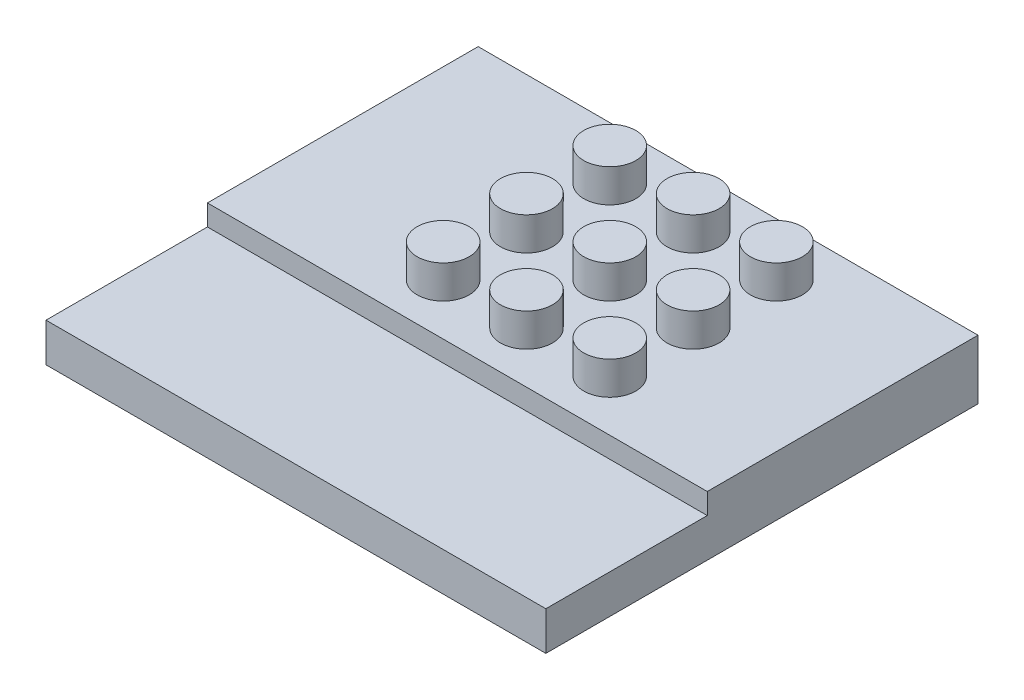
SolidWorks part; units mm, degrees
ref_plane "Front Plane" through (0, 0, 0) normal (0, 0, 1) x (1, 0, 0)
ref_plane "Top Plane" through (0, 0, 0) normal (0, 1, 0) x (1, 0, 0)
ref_plane "Right Plane" through (0, 0, 0) normal (1, 0, 0) x (0, 0, -1)
ref_plane "Plane2" through (0, 1.5875, 0) normal (0, 1, 0) x (-1, 0, 0)
sketch "Sketch3" plane through (0, 1.5875, 0) normal (0, 1, 0) x (-1, 0, 0)
  line L1 (-10.75, -16) -> (-17.5, -16)
  line L2 (-10.75, -16) -> (-10.75, -26.25)
  line L3 (-10.75, -26.25) -> (-17.5, -26.25)
  line L4 (-17.5, -16) -> (-17.5, -26.25)
extrude "Boss-Extrude2" add sketch "Sketch3" along normal blind 4.4125
sketch "Sketch5" plane through (0, 1.5875, 0) normal (0, -1, 0) x (1, 0, 0)
  circle A0 centre (16.36, -24.96) radius 1.25
  circle A1 centre (12.36, -24.96) radius 1.25
  circle A2 centre (8.36, -24.96) radius 1.25
  circle A3 centre (16.36, -20.96) radius 1.25
  circle A4 centre (12.36, -20.96) radius 1.25
  circle A5 centre (8.36, -20.96) radius 1.25
  circle A6 centre (16.36, -16.96) radius 1.25
  circle A7 centre (12.36, -16.96) radius 1.25
  circle A8 centre (8.36, -16.96) radius 1.25
  dimension "D1" = 3
  dimension "D2" = 3
extrude "Boss-Extrude3" add sketch "Sketch5" along normal blind 1.5875 and the other way blind 6
sketch "Sketch6" plane through (17.5, 0, 0) normal (1, 0, 0) x (0, 0, -1)
  line L0 (16, 6) -> (16.4473, 6) construction
  line L1 (6.75, 6) -> (27.5, 6)
  line L2 (6.75, 6) -> (6.75, 3.1425)
  line L3 (6.75, 3.1425) -> (27.5, 3.1425)
  line L4 (27.5, 6) -> (27.5, 3.1425)
extrude "Boss-Extrude4" add sketch "Sketch6" along normal blind 6
sketch "Sketch7" plane through (10.75, 0, 0) normal (-1, 0, 0) x (0, 0, 1)
  line L1 (-27.5, 6) -> (-6.75, 6)
  line L2 (-27.5, 6) -> (-27.5, 3.1425)
  line L3 (-27.5, 3.1425) -> (-6.75, 3.1425)
  line L4 (-6.75, 6) -> (-6.75, 3.1425)
extrude "Boss-Extrude5" add sketch "Sketch7" along normal blind 11.25
sketch "Sketch9" plane through (17.5, 0, 0) normal (-1, 0, 0) x (0, 0, 1)
  line L1 (-16, 6) -> (-6.75, 6)
  line L2 (-16, 6) -> (-16, 3.1425)
  line L3 (-16, 3.1425) -> (-6.75, 3.1425)
  line L4 (-6.75, 6) -> (-6.75, 3.1425)
extrude "Boss-Extrude6" add sketch "Sketch9" along normal up to next
sketch "Sketch10" plane through (17.5, 0, 0) normal (-1, 0, 0) x (0, 0, 1)
  line L1 (-27.5, 6) -> (-26.25, 6)
  line L2 (-27.5, 6) -> (-27.5, 3.1425)
  line L3 (-27.5, 3.1425) -> (-26.25, 3.1425)
  line L4 (-26.25, 6) -> (-26.25, 3.1425)
extrude "Boss-Extrude7" add sketch "Sketch10" along normal up to next
sketch "Sketch11" plane through (0, 0, 0) normal (0, -1, 0) x (1, 0, 0)
  line L1 (5.3068, -27.8263) -> (10.2105, -27.8263)
  line L2 (5.3068, -27.8263) -> (5.3068, -14.0312)
  line L3 (5.3068, -14.0312) -> (10.2105, -14.0312)
  line L4 (10.2105, -27.8263) -> (10.2105, -14.0312)
extrude "Cut-Extrude1" cut sketch "Sketch11" against normal blind 3.1425
sketch "Sketch12" plane through (0, 6, 0) normal (0, 1, 0) x (1, 0, 0)
  line L1 (-0.9882, 14.5) -> (23.8217, 14.5)
  line L2 (-0.9882, 14.5) -> (-0.9882, 5.7304)
  line L3 (-0.9882, 5.7304) -> (23.8217, 5.7304)
  line L4 (23.8217, 14.5) -> (23.8217, 5.7304)
  line L5 (-0.946, 27.5) -> (23.8172, 27.5)
  line L6 (-0.946, 27.5) -> (-0.946, 31.8208)
  line L7 (-0.946, 31.8208) -> (23.8172, 31.8208)
  line L8 (23.8172, 27.5) -> (23.8172, 31.8208)
extrude "Cut-Extrude2" cut sketch "Sketch12" against normal blind 1
